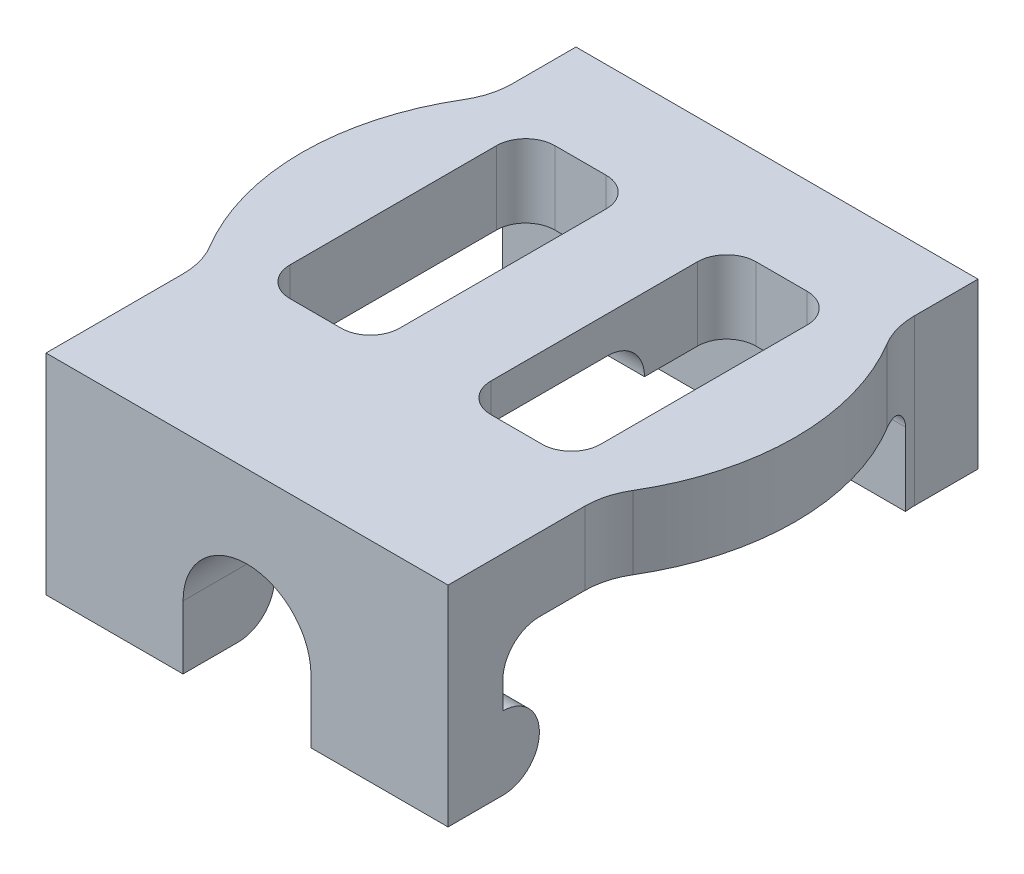
SolidWorks part; units mm, degrees
ref_plane "Front Plane" through (0, 0, 0) normal (0, 0, 1) x (1, 0, 0)
ref_plane "Top Plane" through (0, 0, 0) normal (0, 1, 0) x (1, 0, 0)
ref_plane "Right Plane" through (0, 0, 0) normal (1, 0, 0) x (0, 0, -1)
sketch "Sketch1" plane through (0, 0, 0) normal (0, 1, 0) x (1, 0, 0)
  line L1 (-5.5, -7.25) -> (5.5, -7.25)
  line L2 (-5.5, -7.25) -> (-5.5, 7.25)
  line L3 (-5.5, 7.25) -> (5.5, 7.25)
  line L4 (5.5, -7.25) -> (5.5, 7.25)
  line L5 (-5.5, -7.25) -> (5.5, 7.25) construction
  line L6 (-5.5, 7.25) -> (5.5, -7.25) construction
  point P0 (0, 0)
  dimension "D1" = 11
  dimension "D2" = 14.5
extrude "Boss-Extrude1" add sketch "Sketch1" along normal blind 2
sketch "Sketch4" plane through (5.5, 0, 0) normal (1, 0, 0) x (0, 0, -1)
  line L0 (-7.25, 0) -> (-7.25, -3.7321)
  line L1 (-7.25, -3.7321) -> (-5.75, -3.7321)
  line L2 (-5.75, -1.7321) -> (-8.9382, -1.7321) construction
  line L3 (-5.75, -1.7321) -> (-5.75, 0)
  line L4 (-7.25, 0) -> (7.25, 0) construction
  line L5 (-7.25, 0) -> (-5.75, 0)
  arc A0 (-5.75, -3.7321) -> (-5.75, -1.7321) centre (-5.75, -2.7321) ccw
  circle A1 centre (-4.75, -1) radius 1 construction
  dimension "D2" = 1
  dimension "D4" = 2
  dimension "D3" = 1.5
extrude "Boss-Extrude3" add sketch "Sketch4" against normal up to surface (11 mm away) up to face at (-5.5, 1, 0)
sketch "Sketch5" plane through (0, 0, 7.25) normal (0, 0, 1) x (1, 0, 0)
  line L0 (-5.5, 2) -> (5.5, 2) construction
  line L1 (-1.75, -2) -> (-1.75, -3.7321)
  line L2 (-5.5, -3.7321) -> (5.5, -3.7321) construction
  line L3 (-1.75, -3.7321) -> (1.75, -3.7321)
  line L4 (1.75, -3.7321) -> (1.75, -2)
  circle A0 centre (0, -2) radius 1.75
  line M3 (-5.5, -3.7321) -> (5.5, -3.7321)
  dimension "D1" = 3.5
  dimension "D2" = 4
extrude "Cut-Extrude1" cut sketch "Sketch5" against normal up to next contours A0 L1 L4 M3 | A0 | A0 L4 M3
sketch "Sketch6" plane through (0, 0, 0) normal (0, -1, 0) x (1, 0, 0)
  line L0 (5.5, 5.75) -> (5.5, -7.25) construction
  line L1 (-5.5, -7.25) -> (5.5, -7.25)
  line L2 (-5.5, -7.25) -> (-5.5, -5.25)
  line L3 (-5.5, -5.25) -> (5.5, -5.25)
  line L4 (5.5, -7.25) -> (5.5, -5.25)
  dimension "D1" = 2
extrude "Boss-Extrude4" add sketch "Sketch6" along normal blind 2.5
sketch "Sketch7" plane through (0, 2, 0) normal (0, 1, 0) x (1, 0, 0)
  line L5 (0, 0) -> (0, 4.4646) construction
  line L6 (-4.25, -2.625) -> (-1.25, -2.625)
  line L7 (-4.25, -2.625) -> (-4.25, 4.625)
  line L8 (-4.25, 4.625) -> (-1.25, 4.625)
  line L9 (-1.25, -2.625) -> (-1.25, 4.625)
  line L10 (-4.25, -2.625) -> (-1.25, 4.625) construction
  line L11 (-4.25, 4.625) -> (-1.25, -2.625) construction
  line L12 (1.25, -2.625) -> (4.25, -2.625)
  line L13 (1.25, -2.625) -> (1.25, 4.625)
  line L14 (1.25, 4.625) -> (4.25, 4.625)
  line L15 (4.25, -2.625) -> (4.25, 4.625)
  line L16 (1.25, -2.625) -> (4.25, 4.625) construction
  line L17 (1.25, 4.625) -> (4.25, -2.625) construction
  point P0 (-2.75, 1)
  point P5 (2.75, 1)
  dimension "D1" = 3
  dimension "D2" = 7.25
  dimension "D3" = 5.5
  dimension "D4" = 1
extrude "Cut-Extrude2" cut sketch "Sketch7" against normal up to next
sketch "Sketch8" plane through (0, 2, 0) normal (0, 1, 0) x (1, 0, 0)
  line L0 (-4.25, -2.625) -> (4.25, 4.625) construction
  line L1 (-4.25, -2.625) -> (-1.25, -2.625) construction
  line L2 (-4.25, 4.625) -> (-4.25, -2.625) construction
  line L3 (5.5, 7.25) -> (-5.5, 7.25) construction
  line L4 (5.5, -7.25) -> (5.5, 7.25) construction
  line L5 (-5.5, 7.25) -> (-5.5, -7.25) construction
  line L6 (5.5, 7.25) -> (-5.5, 7.25)
  line L7 (5.5, -7.25) -> (5.5, 7.25)
  line L8 (-5.5, 7.25) -> (-5.5, -7.25)
  circle A0 centre (0, 1) radius 6.75
  dimension "D1" = 13.5
extrude "Boss-Extrude5" add sketch "Sketch8" against normal up to surface (2 mm away) contours L8 A0 | L7 A0 up to face at (-2.75, 0, -1)
fillet "Fillet1" radius 2 3 edges at (5.5, 1, -4.9131) (-5.5, 1, -4.9131) (-5.5, 1, 2.9131)
fillet "Fillet3" radius 0.5 1 edges at (0, 0, -5.25)
fillet "Fillet4" radius 1 1 edges at (0, 0, 5.75)
sketch "Sketch9" plane through (0, 0, 0) normal (0, -1, 0) x (1, 0, 0)
  line L0 (1.25, -4.625) -> (1.25, 2.625) construction
  line L1 (-1.25, 2.625) -> (1.25, 2.625)
  line L2 (-1.25, 2.625) -> (-1.25, -2.375)
  line L3 (-1.25, -2.375) -> (1.25, -2.375)
  line L4 (1.25, 2.625) -> (1.25, -2.375)
  dimension "D1" = 5
extrude "Cut-Extrude3" cut sketch "Sketch9" against normal blind 1
fillet "Fillet5" radius 1 1 edges at (0, 1, -2.375)
fillet "Fillet6" radius 0.4 1 edges at (0, 1, 2.625)
fillet "Fillet7" radius 0.8 8 edges at (4.25, 1, 2.625) (4.25, 1, -4.625) (1.25, 1.3, 2.625) (1.25, 1, -4.625) (-1.25, 1.3, 2.625) (-4.25, 1, 2.625) (-4.25, 1, -4.625) (-1.25, 1, -4.625)
